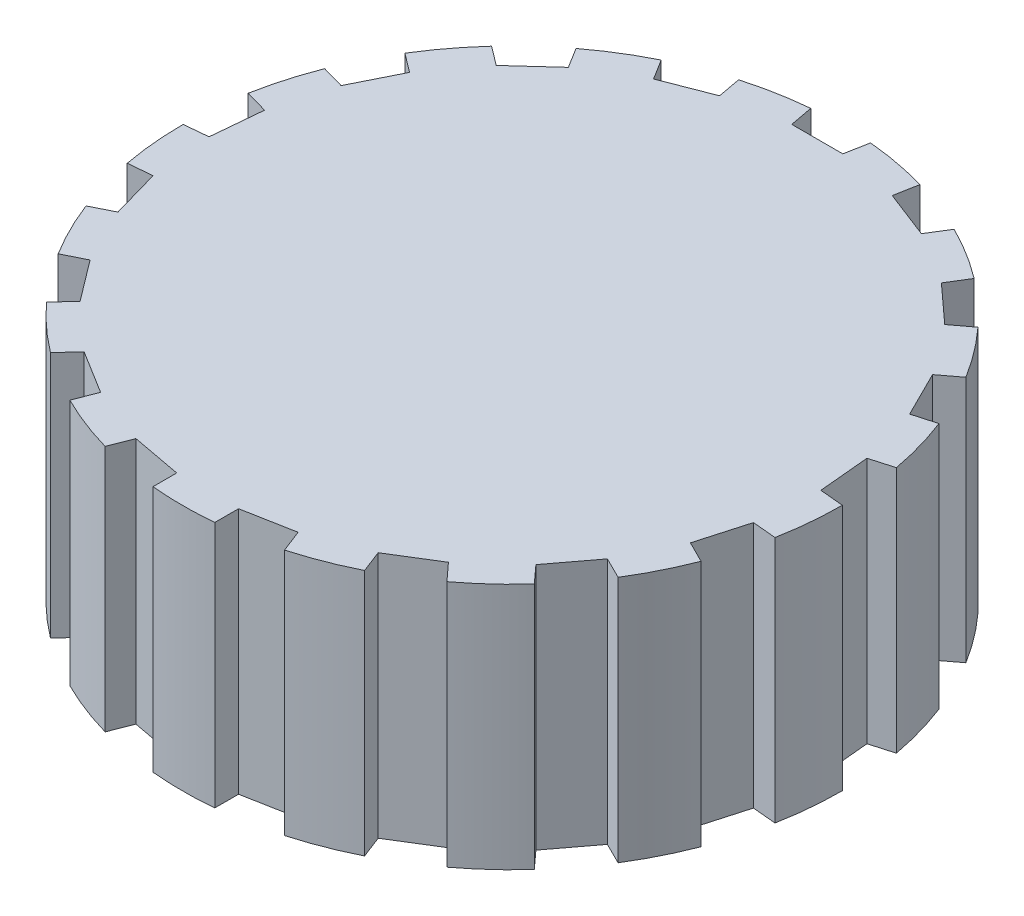
SolidWorks part; units mm, degrees
ref_plane "Front Plane" through (0, 0, 0) normal (0, 0, 1) x (1, 0, 0)
ref_plane "Top Plane" through (0, 0, 0) normal (0, 1, 0) x (1, 0, 0)
ref_plane "Right Plane" through (0, 0, 0) normal (1, 0, 0) x (0, 0, -1)
sketch "Sketch5" plane through (0, 0, 0) normal (0, 1, 0) x (1, 0, 0)
  circle A0 centre (0, 0) radius 25.4
  point P2 (0, 0)
extrude "Boss-Extrude2" add sketch "Sketch5" along normal blind 19.05
sketch "Sketch8" plane through (0, 19.05, 0) normal (0, 1, 0) x (1, 0, 0)
  line L0 (0.0089, 25.4) -> (2.333, 25.4)
  line L1 (0.0089, 25.4) -> (-2.3152, 25.4)
  line L2 (-1.9568, 23.495) -> (1.9746, 23.495)
  line L3 (2.333, 25.4) -> (1.9746, 23.495)
  line L4 (-2.3152, 25.4) -> (-1.9568, 23.495)
  circle A0 centre (0, 0) radius 25.4 construction
  point P0 (0, 25.4)
  point P1 (0, 0)
  point P4 (0, 0)
  dimension "D1" = 25.4
  dimension "D2" = 1.905
extrude "Cut-Extrude1" cut sketch "Sketch8" against normal blind 22.05
pattern_circular "CirPattern1" count 17 over 360 about axis through (0, 19.05, 0) along (0, 1, 0) of "Cut-Extrude1"
